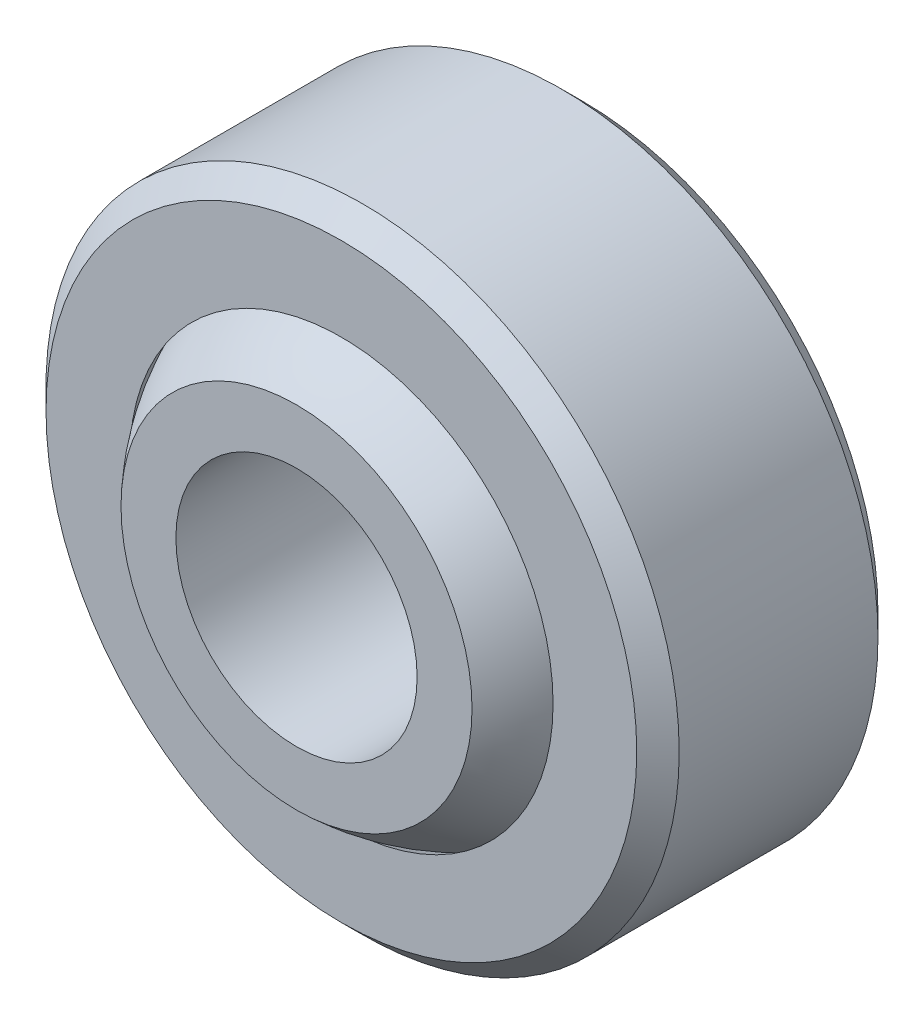
SolidWorks part; units mm, degrees
note: '?' marks a value the reader was unsure of.
ref_plane "Front" through (0, 0, 0) normal (0, 0, 1) x (1, 0, 0)
ref_plane "Top" through (0, 0, 0) normal (0, 1, 0) x (1, 0, 0)
ref_plane "Right" through (0, 0, 0) normal (1, 0, 0) x (0, 0, -1)
sketch "Sketch1" plane through (0, 0, 0) normal (0, 0, 1) x (1, 0, 0)
  circle A0 centre (0, 0) radius 3.175 construction
  circle A1 centre (0, 0) radius 6.35 construction
  circle A2 centre (0, 0) radius 6.4135 construction
  circle A3 centre (0, 0) radius 8.3337
  dimension "D OD" = 16.6675
  dimension "B Hole Dia" = 6.35
  dimension "Ball Dia" = 12.7
  dimension "D1" = 12.827
extrude "Extrude1" add sketch "Sketch1" along normal mid plane 6.35
sketch "Sketch2" plane through (0, 0, 0) normal (0, 0, 1) x (1, 0, 0)
  line L0 (0, 6.4135) -> (0, -6.4135)
  line L1 (0, 6.4135) -> (0, 8.3337) construction
  circle A0 centre (0, 0) radius 6.4135 construction
  arc A1 (0, -6.4135) -> (0, 6.4135) centre (0, 0) ccw
  circle A2 centre (0, 0) radius 8.3337 construction
revolve "Cut-Revolve1" cut sketch "Sketch2" angle 360 about L1
sketch "Sketch3" plane through (0, 0, 0) normal (0, 0, 1) x (1, 0, 0)
  line L0 (0, 6.35) -> (0, -6.35)
  line L1 (0, 6.35) -> (0, 8.3337) construction
  circle A0 centre (0, 0) radius 6.35 construction
  arc A1 (0, -6.35) -> (0, 6.35) centre (0, 0) ccw
  circle A2 centre (0, 0) radius 8.3337 construction
revolve "Revolve1" add sketch "Sketch3" angle 360 about L1
sketch "Sketch4" plane through (0, 0, 0) normal (0, 0, 1) x (1, 0, 0)
  circle A0 centre (0, 0) radius 3.175 construction
  circle A1 centre (0, 0) radius 3.175
extrude "Cut-Extrude1" cut sketch "Sketch4" against normal through all and the other way through all
sketch "Sketch5" plane through (0, 0, 0) normal (1, 0, 0) x (0, 0, -1)
  line L0 (-4.3561, 8.3337) -> (4.3561, 8.3337) construction
  line L1 (-4.3561, 8.3337) -> (-5.4993, 8.3337)
  line L2 (-4.3561, 8.3337) -> (-4.3561, -8.3337)
  line L3 (-4.3561, -8.3337) -> (-5.4993, -8.3337)
  line L4 (-5.4993, 8.3337) -> (-5.4993, -8.3337)
  line L5 (4.3561, -8.3337) -> (5.4993, -8.3337)
  line L6 (4.3561, -8.3337) -> (4.3561, 8.3337)
  line L7 (4.3561, 8.3337) -> (5.4993, 8.3337)
  line L8 (5.4993, -8.3337) -> (5.4993, 8.3337)
  line L16 (3.175, 8.3337) -> (-3.175, 8.3337) construction
  line L17 (5.4993, -3.175) -> (5.4993, 3.175) construction
  line L18 (-5.4993, -3.175) -> (-5.4993, 3.175) construction
  line L19 (-4.3561, -8.3337) -> (4.3561, -8.3337) construction
  line L20 (-3.175, -8.3337) -> (3.175, -8.3337) construction
  line L21 (0, 0) -> (-4.3561, 1.0458) construction
  line L22 (0, 0) -> (-4.3561, -1.0458) construction
  dimension "W ball Width" = 8.7122
  dimension "Mis Angle" = 27
extrude "Cut-Extrude2" cut sketch "Sketch5" against normal through all and the other way through all
chamfer "Chamfer1" distance 0.5588 angle 45 2 edges at (8.3337, 0, 3.175) (8.3337, 0, -3.175)
sketch "Sketch7" plane through (0, 0, 0) normal (1, 0, 0) x (0, 0, -1)
  line L0 (0, 0) -> (-4.3561, -1.0458) construction
  line L1 (0, 0) -> (-4.3561, 1.0458) construction
  line L2 (0, 0) -> (-4.3561, -1.0458) construction
  line L3 (0, 0) -> (-4.3561, 1.0458) construction
  line L4 (4.3561, 3.175) -> (-4.3561, 3.175)
  line L5 (-4.3561, -3.175) -> (4.3561, -3.175)
  line L6 (-4.3561, -3.175) -> (4.3561, -3.175) construction
  line L7 (4.3561, 3.175) -> (-4.3561, 3.175) construction
  arc A0 (3.175, 5.5725) -> (-3.175, 5.5725) centre (0, 0) ccw
  arc A1 (-3.175, -5.5725) -> (3.175, -5.5725) centre (0, 0) ccw
  arc A2 (-3.175, -5.5725) -> (3.175, -5.5725) centre (0, 0) ccw construction
  arc A3 (3.175, 5.5725) -> (-3.175, 5.5725) centre (0, 0) ccw construction
ref_axis "Center Axis 1" through (0, 0, -3.9256) along (0, 0, 1)?
ref_plane "Contact Plane 1" through (0, 0, 4.3561) normal (0, 0, 1) x (1, 0, 0)
ref_plane "Contact Plane 2" through (0, 0, -4.3561) normal (0, 0, -1) x (-1, 0, 0)
equation "\"D1@Sketch1\"=\"Ball Dia@Sketch1\"*1.01"
